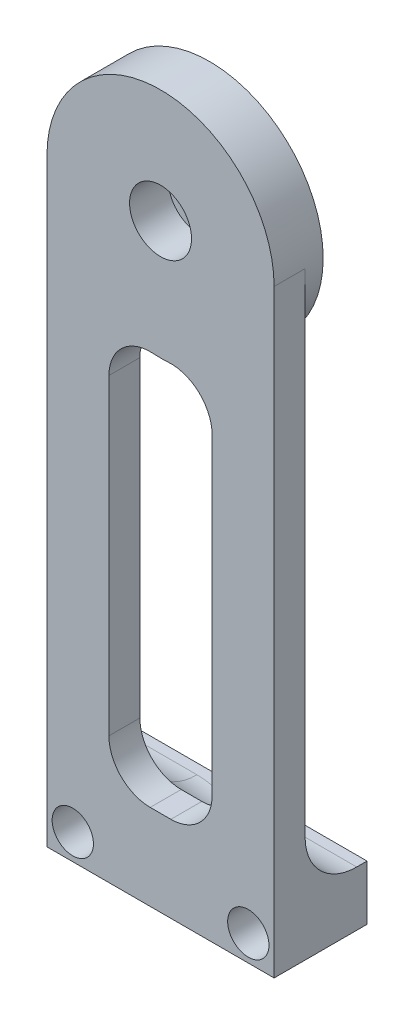
SolidWorks part; units mm, degrees
ref_plane "Front Plane" through (0, 0, 0) normal (0, 0, 1) x (1, 0, 0)
ref_plane "Top Plane" through (0, 0, 0) normal (0, 1, 0) x (1, 0, 0)
ref_plane "Right Plane" through (0, 0, 0) normal (1, 0, 0) x (0, 0, -1)
sketch "Sketch1" plane through (0, 0, 0) normal (0, 0, 1) x (1, 0, 0)
  line L0 (0, 29) -> (0, -29) construction
  line L1 (-11, 29) -> (-11, -29)
  line L2 (11, 29) -> (11, -29)
  line L3 (-11, -29) -> (11, -29)
  line L5 (-11, -29) -> (11, -29)
  line L6 (-11, -29) -> (-11, -23.69)
  line L7 (-11, -23.69) -> (11, -23.69)
  line L8 (11, -29) -> (11, -23.69)
  line L10 (-5, 18.6438) -> (-5, -20.69)
  line L11 (-5, -20.69) -> (5, -20.69)
  line L12 (5, 18.6438) -> (5, -20.69)
  circle A0 centre (0, 29) radius 11
  arc A2 (-5, 18.6438) -> (5, 18.6438) centre (0, 29) ccw
  point P8 (0, 0)
  dimension "D2" = 22
  dimension "D6" = 6
  dimension "D7" = 11.5
  dimension "D1" = 58
  dimension "D3" = 5.31
  dimension "D4" = 3
  dimension "D5" = 6
extrude "Boss-Extrude1" add sketch "Sketch1" along normal blind 3 contours A0 | L0 A0 L1 | A0 L0 L2 | L6 L5 L8 L7 region at (0, 17.9429, 0) region at (0, 29, 0)
extrude "Boss-Extrude2" add sketch "Sketch1<3>" against normal blind 1.75 contours A0 region at (0, 29, 0)
sketch "Sketch1<3>" plane through (0, 0, 0) normal (0, 0, 1) x (1, 0, 0) same geometry as "Sketch1"
sketch "Sketch2" plane through (0, 0, 3) normal (0, 0, 1) x (1, 0, 0)
  circle A0 centre (0, 29) radius 1.75
  circle A3 centre (0, 29) radius 3
  dimension "D1" = 3.5
  dimension "D2" = 6
extrude "Cut-Extrude1" cut sketch "Sketch2" against normal up to surface (4.75 mm away) contours A0 region at (0, 29, 3) up to face at (11, 29, -1.75)
extrude "Cut-Extrude2" cut sketch "Sketch2<3>" against normal offset from surface (3.75 mm away) 1 contours A3 A0 region at (-2.9151, 29, 3) up to face at (1.75, 29, -1.75)
sketch "Sketch2<3>" plane through (0, 0, 3) normal (0, 0, 1) x (1, 0, 0) same geometry as "Sketch2"
extrude "Boss-Extrude3" add sketch "Sketch1<6>" against normal blind 6 contours L7 L0 L5 L2 | L0 L7 L1 L3 region at (-5.5, -26.345, 0) region at (5.5, -26.345, 0)
sketch "Sketch1<6>" plane through (0, 0, 0) normal (0, 0, 1) x (1, 0, 0) same geometry as "Sketch1"
sketch "Sketch3" plane through (0, 0, 3) normal (0, 0, 1) x (1, 0, 0)
  line L1 (-8.5, -26.505) -> (8.5, -26.505) construction
  line L2 (-11, -29) -> (11, -29) construction
  circle A1 centre (-8.5, -26.505) radius 1.1
  circle A2 centre (8.5, -26.505) radius 1.1
  circle A3 centre (-8.5, -26.505) radius 2
  circle A4 centre (8.5, -26.505) radius 2
  point P5 (0, -26.505)
  dimension "D2" = 2.2
  dimension "D3" = 4
  dimension "D4" = 2.495
  dimension "D1" = 17
extrude "Cut-Extrude3" cut sketch "Sketch3" against normal up to surface (9 mm away) contours A1 | A2 region at (-8.5, -26.505, 3) up to face at (0, -26.345, -6)
extrude "Cut-Extrude4" cut sketch "Sketch3<3>" against normal offset from surface (8 mm away) 1 up to face at (-7.4, -26.505, -6)
sketch "Sketch3<3>" plane through (0, 0, 3) normal (0, 0, 1) x (1, 0, 0) same geometry as "Sketch3"
fillet "Filete1" radius 4 4 edges at (5, 18.6438, 1.5) (-5, 18.6438, 1.5) (5, -20.69, 1.5) (-5, -20.69, 1.5)
fillet "Filete2" radius 5 1 edges at (0, -23.69, 0)
